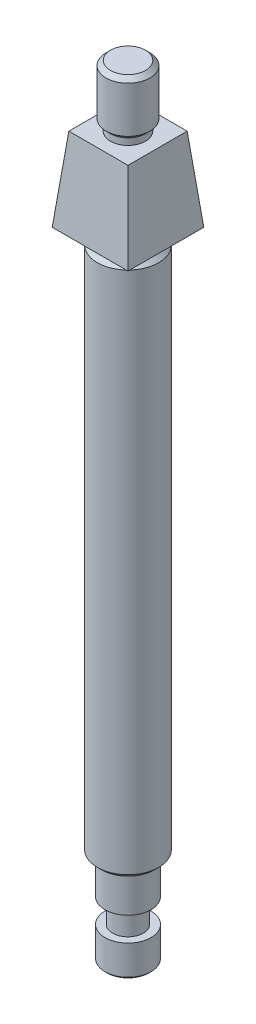
SolidWorks part; units mm, degrees
material "1.0050 (E295)"
ref_plane "Front Plane" through (0, 0, 0) normal (0, 0, 1) x (1, 0, 0)
ref_plane "Top Plane" through (0, 0, 0) normal (0, 1, 0) x (1, 0, 0)
ref_plane "Right Plane" through (0, 0, 0) normal (1, 0, 0) x (0, 0, -1)
sketch "Sketch1" plane through (0, 0, 0) normal (0, 1, 0) x (1, 0, 0)
  circle A0 centre (0, 0) radius 10.5
  dimension "D1" = 21
extrude "Boss-Extrude1" add sketch "Sketch1" along normal blind 42
sketch "Sketch3" plane through (0, 42, 0) normal (0, 1, 0) x (1, 0, 0)
  circle A0 centre (0, 0) radius 14
  dimension "D1" = 28
extrude "Boss-Extrude2" add sketch "Sketch3" along normal blind 243
sketch "Sketch4" plane through (0, 285, 0) normal (0, 1, 0) x (1, 0, 0)
  circle A0 centre (0, 0) radius 9
  dimension "D1" = 18
extrude "Boss-Extrude3" add sketch "Sketch4" along normal blind 5
sketch "Sketch5" plane through (0, 290, 0) normal (0, 1, 0) x (1, 0, 0)
  line L1 (-17.3, -17.3) -> (17.3, -17.3)
  line L2 (-17.3, -17.3) -> (-17.3, 17.3)
  line L3 (-17.3, 17.3) -> (17.3, 17.3)
  line L4 (17.3, -17.3) -> (17.3, 17.3)
  line L5 (-17.3, -17.3) -> (17.3, 17.3) construction
  line L6 (-17.3, 17.3) -> (17.3, -17.3) construction
  point P0 (0, 0)
  dimension "D1" = 34.6
  dimension "D2" = 34.6
extrude "Boss-Extrude4" add sketch "Sketch5" along normal blind 38 draft 5.711
sketch "Sketch6" plane through (0, 328, 0) normal (0, 1, 0) x (1, 0, 0)
  circle A0 centre (0, 0) radius 8
  dimension "D1" = 16
extrude "Boss-Extrude6" add sketch "Sketch6" along normal blind 3 contours A0
sketch "Sketch7" plane through (0, 331, 0) normal (0, 1, 0) x (1, 0, 0)
  circle A0 centre (0, 0) radius 10
  dimension "D1" = 20
extrude "Boss-Extrude7" add sketch "Sketch7" along normal blind 25
chamfer "Chamfer1" distance 2 angle 45 2 edges at (0, 331, 10) (0, 356, 10)
fillet "Fillet2" radius 2.5 2 edges at (0, 285, 9) (0, 290, 9)
sketch "Sketch8" plane through (0, 0, 0) normal (0, 0, 1) x (1, 0, 0)
  line L0 (-10.5, 42) -> (-10.5, 0) construction
  line L1 (-10.5, 25.5) -> (-7, 25.5)
  line L2 (-10.5, 25.5) -> (-10.5, 14.5)
  line L3 (-10.5, 14.5) -> (-7, 14.5)
  line L4 (-7, 25.5) -> (-7, 14.5)
  line L5 (-14, 42) -> (14, 42) construction
  point P6 (-10.5, 20)
  dimension "D1" = 11
  dimension "D2" = 7
  dimension "D3" = 22
revolve "Cut-Revolve1" cut sketch "Sketch8" angle 360 about axis through (0, 42, 0) along (0, -1, 0)
chamfer "Chamfer2" distance 2 angle 45 2 edges at (0, 42, 14) (0, 285, 14)
chamfer "Chamfer3" distance 1 angle 45 1 edges at (0, 0, 10.5)
equation "\"D3@Boss-Extrude4\"=atn(0.1)"
